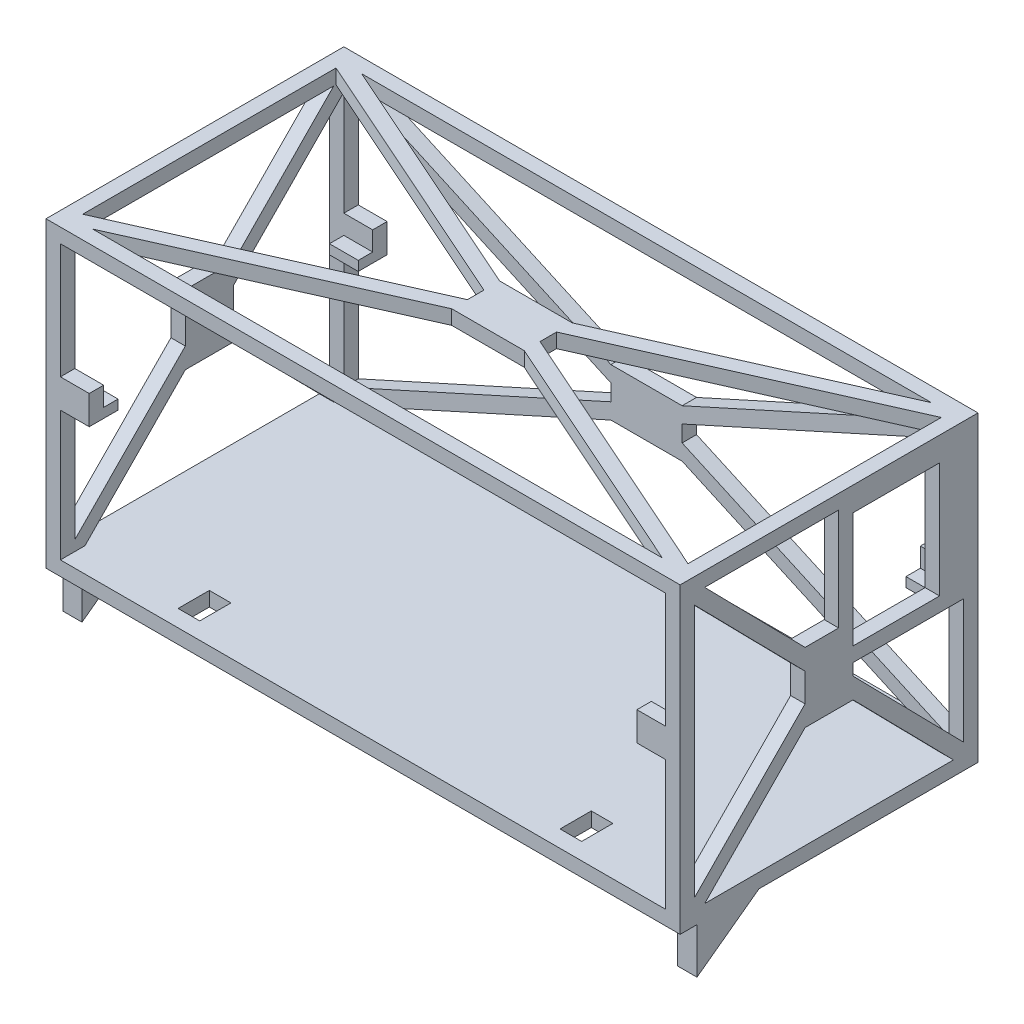
SolidWorks part; units mm, degrees
note: The reader was unsure of these and kept them because the rebuilt part matched: shared geometry of "Sketch6<3>", "Sketch7<4>".
ref_plane "Front Plane" through (0, 0, 0) normal (0, 0, 1) x (1, 0, 0)
ref_plane "Top Plane" through (0, 0, 0) normal (0, 1, 0) x (1, 0, 0)
ref_plane "Right Plane" through (0, 0, 0) normal (1, 0, 0) x (0, 0, -1)
sketch "Sketch1" plane through (0, 0, 0) normal (0, 1, 0) x (1, 0, 0)
  line L1 (-33, 15.5) -> (33, 15.5)
  line L2 (-33, 15.5) -> (-33, -15.5)
  line L3 (-33, -15.5) -> (33, -15.5)
  line L4 (33, 15.5) -> (33, -15.5)
  line L5 (-33, 15.5) -> (33, -15.5) construction
  line L6 (-33, -15.5) -> (33, 15.5) construction
  point P0 (0, 0)
  dimension "D1" = 66
  dimension "D2" = 31
extrude "Boss-Extrude1" add sketch "Sketch1" along normal blind 31.5
shell "Shell1" thickness 1.5
sketch "Sketch3" plane through (0, 0, -15.5) normal (0, 0, -1) x (-1, 0, 0)
  line L4 (31.5, 30) -> (31.5, 1.5) construction
  line L8 (-31.5, 30) -> (31.5, 1.5) construction
  line L19 (-31.5, 1.5) -> (31.5, 30) construction
  line L20 (-31.5, 29.1768) -> (29.6804, 1.5)
  line L24 (-29.6804, 1.5) -> (31.5, 29.1768)
  line L25 (-31.5, 30) -> (31.5, 30) construction
  line L26 (-31.5, 30) -> (-31.5, 1.5) construction
  line L27 (-31.5, 1.5) -> (31.5, 1.5) construction
  line L29 (-31.5, 1.5) -> (31.5, 1.5)
  line L30 (31.5, 1.5) -> (31.5, 30)
  line L31 (31.5, 30) -> (-31.5, 30)
  line L32 (-31.5, 30) -> (-31.5, 1.5)
  line L33 (-29.6804, 30) -> (31.5, 2.3232)
  line L34 (-31.5, 2.3232) -> (29.6804, 30)
  line L35 (-31.8091, 29.3167) -> (31.1909, 0.8167) construction
  line L36 (-31.1909, 30.6833) -> (31.8091, 2.1833) construction
  line L37 (-31.8091, 2.1833) -> (31.1909, 30.6833) construction
  line L39 (-31.1909, 0.8167) -> (31.8091, 29.3167) construction
  line L40 (31.5, 30) -> (31.5, 1.5) construction
  line L41 (-31.5, 30) -> (-31.5, 1.5) construction
  line L43 (-3.7067, 18.25) -> (3.7067, 18.25)
  line L44 (-3.7067, 18.25) -> (-3.7067, 13.25)
  line L45 (-3.7067, 13.25) -> (3.7067, 13.25)
  line L46 (3.7067, 18.25) -> (3.7067, 13.25)
  line L47 (-3.7067, 18.25) -> (3.7067, 13.25) construction
  line L48 (-3.7067, 13.25) -> (3.7067, 18.25) construction
  point P5 (-16.5, 1.5)
  point P9 (7.7772, 12.517)
  point P12 (31.2379, 25.7027)
  point P13 (-31.7621, 2.2027)
  point P16 (32.5321, 22.2331)
  point P17 (-30.4679, -1.2669)
  point P43 (0, 15.75)
  dimension "D4" = 5
  dimension "D2" = 0.75
  dimension "D3" = 0.75
extrude "Cut-Extrude1" cut sketch "Sketch3" against normal up to next
sketch "Sketch4" plane through (-31.5, 0, 0) normal (1, 0, 0) x (0, 0, -1)
  line L2 (-14, 30) -> (-14, 1.5)
  line L3 (-14, 30) -> (14, 1.5) construction
  line L10 (-14, 1.5) -> (14, 30) construction
  line L11 (-12.9486, 1.5) -> (14, 28.9298)
  line L12 (-14, 28.9298) -> (12.9486, 1.5)
  line L13 (-14, 2.5702) -> (12.9486, 30)
  line L14 (-12.9486, 30) -> (14, 2.5702)
  line L16 (-15.5, 1.5) -> (14, 1.5)
  line L19 (-15.5, 30) -> (-15.5, 1.5)
  line L22 (14, 30) -> (-15.5, 30)
  line L23 (14, 29.1768) -> (14, 30)
  line L24 (-14, 1.5) -> (14, 1.5)
  line L63 (14, 30) -> (-14, 30)
  line L64 (14, 1.5) -> (14, 30)
  line L67 (-13.465, 30.5256) -> (14.535, 2.0256) construction
  line L68 (-14.535, 29.4744) -> (13.465, 0.9744) construction
  line L69 (-14.535, 2.0256) -> (13.465, 30.5256) construction
  line L70 (-13.465, 0.9744) -> (14.535, 29.4744) construction
  line L71 (-2.5, 19.3648) -> (2.5, 19.3648)
  line L72 (-2.5, 19.3648) -> (-2.5, 12.1352)
  line L73 (-2.5, 12.1352) -> (2.5, 12.1352)
  line L74 (2.5, 19.3648) -> (2.5, 12.1352)
  line L75 (-2.5, 19.3648) -> (2.5, 12.1352) construction
  line L76 (-2.5, 12.1352) -> (2.5, 19.3648) construction
  line L77 (14, 30) -> (-15.5, 30) construction
  line L78 (14, 1.5) -> (-15.5, 1.5) construction
  line L80 (14, 30) -> (14, 29.1768) construction
  line L81 (-15.5, 30) -> (-15.5, 1.5) construction
  line L89 (14, 2.3232) -> (15.5, 2.3232)
  line L90 (15.5, 29.1768) -> (14, 29.1768)
  line L91 (15.5, 2.3232) -> (15.5, 29.1768)
  line L92 (14, 1.5) -> (14, 2.3232)
  point P22 (0, 15.75)
  dimension "D2" = 0.75
  dimension "D3" = 0.75
  dimension "D4" = 5
  dimension "D5" = 1.5
  dimension "D1" = 0
extrude "Cut-Extrude2" cut sketch "Sketch4" against normal up to next and the other way up to next
ref_plane "Plane3" through (0, 15, 0) normal (0, -1, 0) x (-1, 0, 0)
sketch "Sketch6" plane through (0, 15, 0) normal (0, -1, 0) x (-1, 0, 0)
  line L0 (-31.5, 15.5) -> (-31.5, 12.5)
  line L1 (-31.5, 12.5) -> (-28.5, 12.5)
  line L2 (-28.5, 12.5) -> (-28.5, 15.5)
  line L3 (-28.5, 15.5) -> (-31.5, 15.5)
  line L4 (-31.5, 14) -> (-28.5, 14)
  point P11 (-28.5, 14)
  dimension "D1" = 3
extrude "Boss-Extrude4" add sketch "Sketch6" against normal blind 3 contours L0 L4 L2 L3
extrude "Boss-Extrude5" add sketch "Sketch6<3>" against normal offset from surface (1 mm away) 2 contours L4 L0 L1 L2 up to face at (30, 18, -14.75)
sketch "Sketch6<3>" plane through (0, 15, 0) normal (0, -1, 0) x (-1, 0, 0) same geometry as "Sketch6"
ref_plane "Plane4" through (0, 0, 0) normal (0, 0, 1) x (1, 0, 0)
mirror "Mirror2" about plane through (0, 0, 0) normal (0, 0, 1) of "Boss-Extrude4", "Boss-Extrude5"
ref_plane "Plane5" through (0, 0, 0) normal (-1, 0, 0) x (0, 0, 1)
mirror "Mirror3" about plane through (0, 0, 0) normal (-1, 0, 0) of "Mirror2", "Boss-Extrude4", "Boss-Extrude5"
sketch "Sketch7" plane through (31.5, 0, 0) normal (1, 0, 0) x (0, 0, -1)
  line L0 (14, 16) -> (12.5, 16) construction
  line L1 (2.5, 29) -> (11.5, 29)
  line L2 (2.5, 29) -> (2.5, 17)
  line L3 (2.5, 17) -> (11.5, 17)
  line L4 (11.5, 29) -> (11.5, 17)
  line L5 (2.5, 29) -> (11.5, 17) construction
  line L6 (2.5, 17) -> (11.5, 29) construction
  line L7 (14, 28.9298) -> (14, 2.5702) construction
  line L10 (1, 30) -> (1, 15.5)
  line L11 (1, 15.5) -> (14, 15.5)
  line L14 (1, 30) -> (14, 30)
  line L15 (-12.9486, 30) -> (12.9486, 30) construction
  line L16 (14, 30) -> (14, 15.5)
  point P0 (7, 23)
  point P13 (7, 23)
  line M44 (-2.5, 19.3648) -> (2.5, 19.3648)
  line M45 (2.5, 19.3648) -> (12.9486, 30)
  line M46 (12.9486, 30) -> (14, 30)
  line M49 (14, 18) -> (14, 28.9298)
  line M50 (14, 28.9298) -> (2.5, 17.2245)
  line M51 (2.5, 17.2245) -> (2.5, 14.2755)
  line M63 (2.5, 17.2245) -> (2.5, 14.2755)
  dimension "D1" = 12
  dimension "D2" = 9
  dimension "D3" = 1.5
  dimension "D4" = 1.5
  dimension "D5" = 1
  dimension "D6" = 2.5
extrude "Boss-Extrude8" add sketch "Sketch7" along normal up to surface (1.5 mm away) contours L16 L11 L3 L4 M49 M51 M50 | L10 L14 L2 M45 M63 M44 | L4 L14 M45 up to face at (33, 15.75, 8.25)
extrude "Cut-Extrude5" cut sketch "Sketch7<4>" along normal up to surface (1.5 mm away) contours L1 L4 L2 M46 M45 | L4 L2 M46 M50 M45 | L4 L3 M50
sketch "Sketch7<4>" plane through (31.5, 0, 0) normal (1, 0, 0) x (0, 0, -1) same geometry as "Sketch7"
sketch "Sketch10" plane through (0, 30, 0) normal (0, -1, 0) x (1, 0, 0)
  line L0 (-31.5, 13.1793) -> (29.6533, -14)
  line L1 (-31.5, 14) -> (31.5, -14)
  line L2 (-31.5, -14) -> (31.5, 14) construction
  line L3 (-29.6533, -14) -> (31.5, 13.1793)
  line L4 (-29.6533, 14) -> (31.5, -13.1793)
  line L5 (-31.5, -13.1793) -> (29.6533, 14)
  line L7 (-31.1954, 14.6854) -> (31.8046, -13.3146) construction
  line L8 (-31.8046, 13.3146) -> (31.1954, -14.6854) construction
  line L9 (-31.8046, -13.3146) -> (31.1954, 14.6854) construction
  line L10 (-31.1954, -14.6854) -> (31.8046, 13.3146) construction
  line L11 (-31.5, 15.5) -> (31.5, 15.5) construction
  line L13 (-3.7783, 2.5) -> (3.7783, 2.5)
  line L14 (-3.7783, 2.5) -> (-3.7783, -2.5)
  line L15 (-3.7783, -2.5) -> (3.7783, -2.5)
  line L16 (31.5, -14) -> (31.5, -1)
  line L17 (31.5, -1) -> (33, -1)
  line L18 (33, -1) -> (33, 12.9486)
  line L19 (33, 12.9486) -> (31.5, 12.9486)
  line L20 (31.5, 12.9486) -> (31.5, 15.5)
  line L21 (31.5, 15.5) -> (-31.5, 15.5)
  line L22 (-31.5, 15.5) -> (-31.5, 12.9486)
  line L23 (-31.5, 12.9486) -> (-33, 12.9486)
  line L24 (-33, 12.9486) -> (-33, -12.9486)
  line L25 (-33, -12.9486) -> (-31.5, -12.9486)
  line L26 (-31.5, -12.9486) -> (-31.5, -14)
  line L27 (-31.5, -14) -> (-29.6804, -14)
  line L28 (-29.6804, -14) -> (-29.6804, -15.5)
  line L29 (-29.6804, -15.5) -> (29.6804, -15.5)
  line L30 (29.6804, -15.5) -> (29.6804, -14)
  line L31 (29.6804, -14) -> (31.5, -14)
  line L32 (31.5, -14) -> (31.5, 14)
  line L37 (31.5, 14) -> (-31.5, 14)
  line L42 (-31.5, 14) -> (-31.5, -14)
  line L43 (-31.5, -14) -> (31.5, -14)
  line L44 (3.7783, 2.5) -> (3.7783, -2.5)
  line L45 (-3.7783, 2.5) -> (3.7783, -2.5) construction
  line L46 (-3.7783, -2.5) -> (3.7783, 2.5) construction
  point P39 (0, 0)
  line M19 (31.5, -14) -> (31.5, -1)
  line M23 (31.5, 12.9486) -> (31.5, 15.5)
  line M25 (-31.5, 15.5) -> (-31.5, 12.9486)
  line M29 (-31.5, -12.9486) -> (-31.5, -14)
  dimension "D4" = 1.5
  dimension "D5" = 5
  dimension "D1" = 0
  dimension "D2" = 0.75
  dimension "D3" = 0.75
extrude "Cut-Extrude9" cut sketch "Sketch10" against normal up to next contours L42 L5 L14 L0 M25 M29 | L5 L37 L4 L13 | L3 L44 L4 L32 M19 M23 | L3 L43 L0 L15
sketch "Sketch11" plane through (-33, 0, 0) normal (-1, 0, 0) x (0, 0, 1)
  line L0 (13.75, 0) -> (7.2948, 0)
  line L1 (-15.5, 0) -> (15.5, 0) construction
  line L2 (7.2948, 0) -> (13.75, -4.7387)
  line L3 (13.75, -4.7387) -> (13.75, 0)
  line L4 (15.5, 31.5) -> (15.5, 0) construction
  dimension "D1" = 1.75
extrude "Boss-Extrude9" add sketch "Sketch11" against normal blind 2
mirror "Mirror5" about plane through (0, 0, 0) normal (-1, 0, 0) of "Boss-Extrude9"
sketch "Sketch12" plane through (0, 0, 0) normal (0, -1, 0) x (1, 0, 0)
  line L0 (-33, 13.75) -> (33, 13.75) construction
  line L1 (0, 15.5) -> (0, -15.5) construction
  line L2 (-21, 13.75) -> (-18.75, 13.75)
  line L3 (-21, 13.75) -> (-21, 10.5)
  line L4 (-21, 10.5) -> (-18.75, 10.5)
  line L5 (-18.75, 13.75) -> (-18.75, 10.5)
  line L6 (-21, 13.75) -> (-18.75, 10.5) construction
  line L7 (-21, 10.5) -> (-18.75, 13.75) construction
  line L8 (-33, 15.5) -> (33, 15.5) construction
  line L9 (33, -15.5) -> (-33, -15.5) construction
  line L10 (-31, 13.75) -> (-31, 7.2948) construction
  line L11 (21, 13.75) -> (18.75, 13.75)
  line L12 (18.75, 13.75) -> (18.75, 10.5)
  line L13 (21, 13.75) -> (21, 10.5)
  line L14 (21, 10.5) -> (18.75, 10.5)
  point P4 (-19.875, 12.125)
  dimension "D1" = 3.25
  dimension "D2" = 2.25
  dimension "D3" = 10
extrude "Cut-Extrude10" cut sketch "Sketch12" against normal blind 1.5
